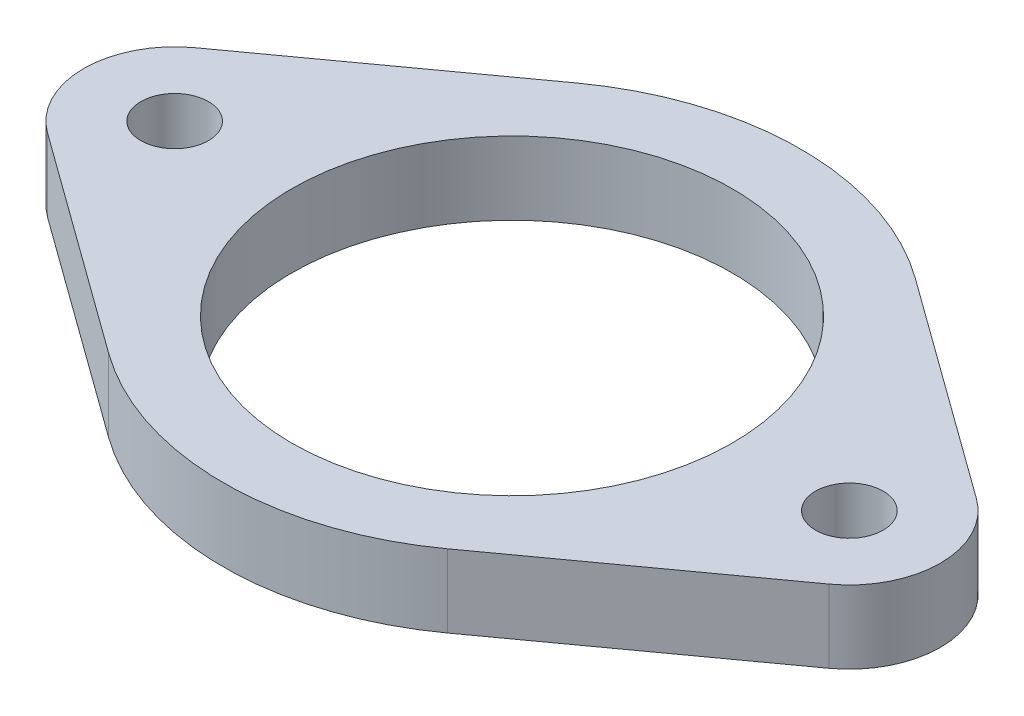
SolidWorks part; units mm, degrees
material "Free-Cutting Brass, UNS C36000"
ref_plane "Front Plane" through (0, 0, 0) normal (0, 0, 1) x (1, 0, 0)
ref_plane "Top Plane" through (0, 0, 0) normal (0, 1, 0) x (1, 0, 0)
ref_plane "Right Plane" through (0, 0, 0) normal (1, 0, 0) x (0, 0, -1)
sketch "Sketch1" plane through (0, 0, 0) normal (0, 1, 0) x (1, 0, 0)
  line L0 (0, 9.5885) -> (0, -9.5885) construction
  line L1 (-14.6812, 0) -> (14.6812, 0) construction
  line L2 (0, 15.5194) -> (21.4376, 0) construction
  line L3 (21.4376, 0) -> (0, -15.5194) construction
  line L4 (0, -15.5194) -> (-21.4376, 0) construction
  line L5 (-21.4376, 0) -> (0, 15.5194) construction
  line L6 (-17.004, 3.2096) -> (-7.3728, 10.182)
  line L7 (7.3728, 10.182) -> (17.004, 3.2096)
  line L8 (-17.004, -3.2096) -> (-7.3728, -10.182)
  line L9 (7.3728, -10.182) -> (17.004, -3.2096)
  circle A0 centre (0, 0) radius 9.5885
  circle A1 centre (14.6812, 0) radius 1.4732
  circle A2 centre (-14.6812, 0) radius 1.4732
  arc A3 (-7.3728, 10.182) -> (7.3728, 10.182) centre (0, -0.0024) cw
  arc A4 (17.004, 3.2096) -> (17.004, -3.2096) centre (14.6805, 0) cw
  arc A5 (-17.004, 3.2096) -> (-17.004, -3.2096) centre (-14.6805, 0) ccw
  arc A6 (-7.3728, -10.182) -> (7.3728, -10.182) centre (0, 0.0024) ccw
  dimension "D1" = 2.9464
  dimension "D2" = 2.9464
  dimension "D3" = 19.177
  dimension "D10" = 12.573
  dimension "D11" = 3.9624
  dimension "D12" = 3.9624
  dimension "D13" = 12.573
  dimension "D4" = 21.4376
  dimension "D5" = 21.4376
  dimension "D6" = 15.5194
  dimension "D7" = 15.5194
  dimension "D8" = 14.6812
  dimension "D9" = 14.6812
extrude "Boss-Extrude1" add sketch "Sketch1" along normal blind 3.175
sketch "Sketch2" plane through (0, 0, 0) normal (0, -1, 0) x (1, 0, 0)
  line L4 (-17.004, 3.2096) -> (-22.1476, -0.514)
  line L5 (-17.004, 3.2096) -> (-7.3728, 10.182) construction
  line L6 (-17.004, 3.2096) -> (0.4843, 15.87)
  arc A5 (7.3728, 10.182) -> (-7.3728, 10.182) centre (0, -0.0024) ccw construction
  dimension "D1" = 6.35
  dimension "D2" = 21.59
ref_point "Point1"
ref_axis "Axis1" through (-14.6812, 0, 0) along (1, 0, 0)
